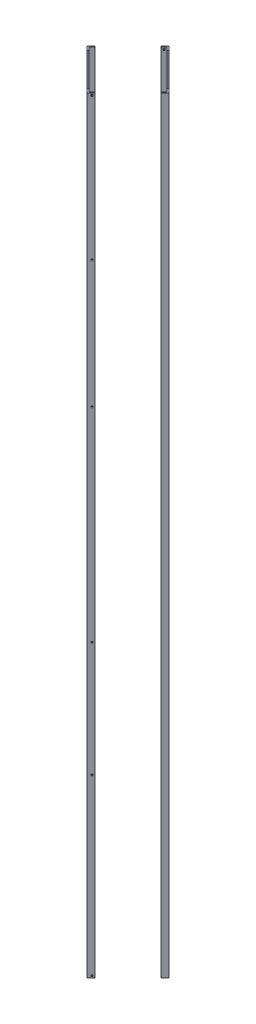
SolidWorks part; units mm, degrees
material "6061-T6 (SS)"
ref_plane "Front Plane" through (0, 0, 0) normal (0, 0, 1) x (1, 0, 0)
ref_plane "Top Plane" through (0, 0, 0) normal (0, 1, 0) x (1, 0, 0)
ref_plane "Right Plane" through (0, 0, 0) normal (1, 0, 0) x (0, 0, -1)
sketch "Sketch2" plane through (0, 0, 0) normal (0, 1, 0) x (1, 0, 0)
  line L0 (0, 94.7743) -> (-8.9803, 85.794)
  line L1 (-8.9803, 85.794) -> (-6.7352, 83.549)
  line L2 (-6.7352, 83.549) -> (0, 90.2842)
  line L3 (0, 90.2842) -> (6.7352, 83.549)
  line L4 (6.7352, 83.549) -> (8.9803, 85.794)
  line L5 (8.9803, 85.794) -> (0, 94.7743)
  line L6 (0, 0) -> (0, 186.644) construction
  line L7 (94.7417, 0.0326) -> (85.7614, 9.0128)
  line L8 (85.7614, 9.0128) -> (83.5164, 6.7678)
  line L9 (83.5164, 6.7678) -> (90.2516, 0.0326)
  line L10 (90.2516, 0.0326) -> (83.5164, -6.7026)
  line L11 (83.5164, -6.7026) -> (85.7614, -8.9477)
  line L12 (85.7614, -8.9477) -> (94.7417, 0.0326)
  line L13 (0, -94.7091) -> (8.9803, -85.7289)
  line L14 (8.9803, -85.7289) -> (6.7352, -83.4838)
  line L15 (6.7352, -83.4838) -> (0, -90.219)
  line L16 (0, -90.219) -> (-6.7352, -83.4838)
  line L17 (-6.7352, -83.4838) -> (-8.9803, -85.7289)
  line L18 (-8.9803, -85.7289) -> (0, -94.7091)
  line L19 (-94.7417, 0.0326) -> (-85.7614, -8.9477)
  line L20 (-85.7614, -8.9477) -> (-83.5164, -6.7026)
  line L21 (-83.5164, -6.7026) -> (-90.2516, 0.0326)
  line L22 (-90.2516, 0.0326) -> (-83.5164, 6.7678)
  line L23 (-83.5164, 6.7678) -> (-85.7614, 9.0128)
  line L24 (-85.7614, 9.0128) -> (-94.7417, 0.0326)
  point P1 (-3.3676, 86.9166)
  point P31 (0, 0.0326)
  dimension "D1" = 127.635
  dimension "D2" = 12.7
  dimension "D3" = 12.7
  dimension "D4" = 3.175
  dimension "D5" = 3.175
  dimension "D7" = 127.635
  dimension "D6" = 4
extrude "Boss-Extrude1" add sketch "Sketch2" along normal blind 1778
sketch "Sketch3" plane through (0, 0, 0) normal (0, -1, 0) x (1, 0, 0)
  circle A0 centre (0, 0) radius 94.7417
sketch "Sketch4" plane through (-47.3546, 0, 47.3546) normal (-0.7071, 0, 0.7071) x (0.7071, 0, 0.7071)
  line L0 (-54.3155, 0) -> (-54.3155, 4.7625)
  line L1 (-54.3155, 1778) -> (-54.3155, 0) construction
  line L2 (-54.3155, 4.7625) -> (-67.0155, 4.7625)
  line L3 (-67.0155, 1778) -> (-67.0155, 0) construction
  line L4 (-67.0155, 0) -> (-54.3155, 0) construction
  circle A0 centre (-59.078, 4.7625) radius 2.0066
  dimension "D2" = 4.0132
  dimension "D3" = 7.9375
  dimension "D4" = 4.7625
  dimension "D1" = 4.7625
extrude "Cut-Extrude1" cut sketch "Sketch4" against normal up to next (3.175 mm away) contours L2 A0 | L2 A0 region at (-89.129, 3.9109, 5.5801) region at (-89.129, 5.6141, 5.5801)
sketch "Sketch5" plane through (-47.3871, 0, -47.3871) normal (-0.7071, 0, -0.7071) x (-0.7071, 0, 0.7071)
  line L0 (-54.3155, 1778) -> (-54.3155, 0) construction
  line L1 (-67.0155, 0) -> (-54.3155, 0)
  line L2 (-67.0155, 0) -> (-67.0155, 4.7625)
  line L3 (-67.0155, 4.7625) -> (-54.3155, 4.7625)
  line L4 (-54.3155, 0) -> (-54.3155, 4.7625)
  line L5 (-67.0155, 1778) -> (-67.0155, 0) construction
  circle A0 centre (-59.078, 4.7625) radius 2.0066
  dimension "D2" = 4.0132
  dimension "D4" = 4.7625
  dimension "D1" = 4.7625
  dimension "D3" = 7.9375
extrude "Cut-Extrude2" cut sketch "Sketch5" against normal up to next (3.175 mm away) contours L3 A0 | L3 A0 region at (-5.6127, 5.6141, -89.1616) region at (-5.6127, 3.9109, -89.1616)
sketch "Sketch6" plane through (47.3871, 0, -47.3871) normal (0.7071, 0, -0.7071) x (-0.7071, 0, -0.7071)
  line L0 (-54.2695, 1778) -> (-54.2695, 0) construction
  line L1 (-66.9695, 0) -> (-54.2695, 0)
  line L2 (-66.9695, 0) -> (-66.9695, 4.7625)
  line L3 (-66.9695, 4.7625) -> (-54.2695, 4.7625)
  line L4 (-54.2695, 0) -> (-54.2695, 4.7625)
  line L5 (-66.9695, 1778) -> (-66.9695, 0) construction
  circle A0 centre (-59.032, 4.7625) radius 2.0066
  dimension "D2" = 4.0132
  dimension "D4" = 4.7625
  dimension "D1" = 4.7625
  dimension "D3" = 7.9375
extrude "Cut-Extrude3" cut sketch "Sketch6" against normal up to next (3.175 mm away) contours L3 A0 | L3 A0 region at (89.129, 5.6141, -5.6452) region at (89.129, 3.9109, -5.6452)
sketch "Sketch7" plane through (47.3546, 0, 47.3546) normal (0.7071, 0, 0.7071) x (0.7071, 0, -0.7071)
  line L0 (-54.2695, 1778) -> (-54.2695, 0) construction
  line L1 (-66.9695, 0) -> (-54.2695, 0)
  line L2 (-66.9695, 0) -> (-66.9695, 4.7625)
  line L3 (-66.9695, 4.7625) -> (-54.2695, 4.7625)
  line L4 (-54.2695, 0) -> (-54.2695, 4.7625)
  line L5 (-66.9695, 1778) -> (-66.9695, 0) construction
  circle A0 centre (-59.032, 4.7625) radius 2.0066
  dimension "D2" = 4.0132
  dimension "D3" = 7.9375
  dimension "D4" = 4.7625
  dimension "D1" = 4.7625
extrude "Cut-Extrude4" cut sketch "Sketch7" against normal up to next (3.175 mm away) contours L3 A0 | L3 A0 region at (5.6127, 5.6141, 89.0965) region at (5.6127, 3.9109, 89.0965)
pattern_linear "LPattern1" count 2 spacing 403.225 along (0, 1, 0) of "Cut-Extrude4", "Cut-Extrude3", "Cut-Extrude1", "Cut-Extrude2"
pattern_linear "LPattern2" count 2 spacing 669.925 along (0, 1, 0) of "Cut-Extrude1", "Cut-Extrude2", "Cut-Extrude3", "Cut-Extrude4"
pattern_linear "LPattern3" count 2 spacing 1143 along (0, 1, 0) of "Cut-Extrude1", "Cut-Extrude2", "Cut-Extrude3", "Cut-Extrude4"
pattern_linear "LPattern4" count 2 spacing 1438.275 along (0, 1, 0) of "Cut-Extrude1", "Cut-Extrude2", "Cut-Extrude3", "Cut-Extrude4"
pattern_linear "LPattern5" count 2 spacing 1768.4775 along (0, 1, 0) of "Cut-Extrude1", "Cut-Extrude2", "Cut-Extrude3", "Cut-Extrude4"
